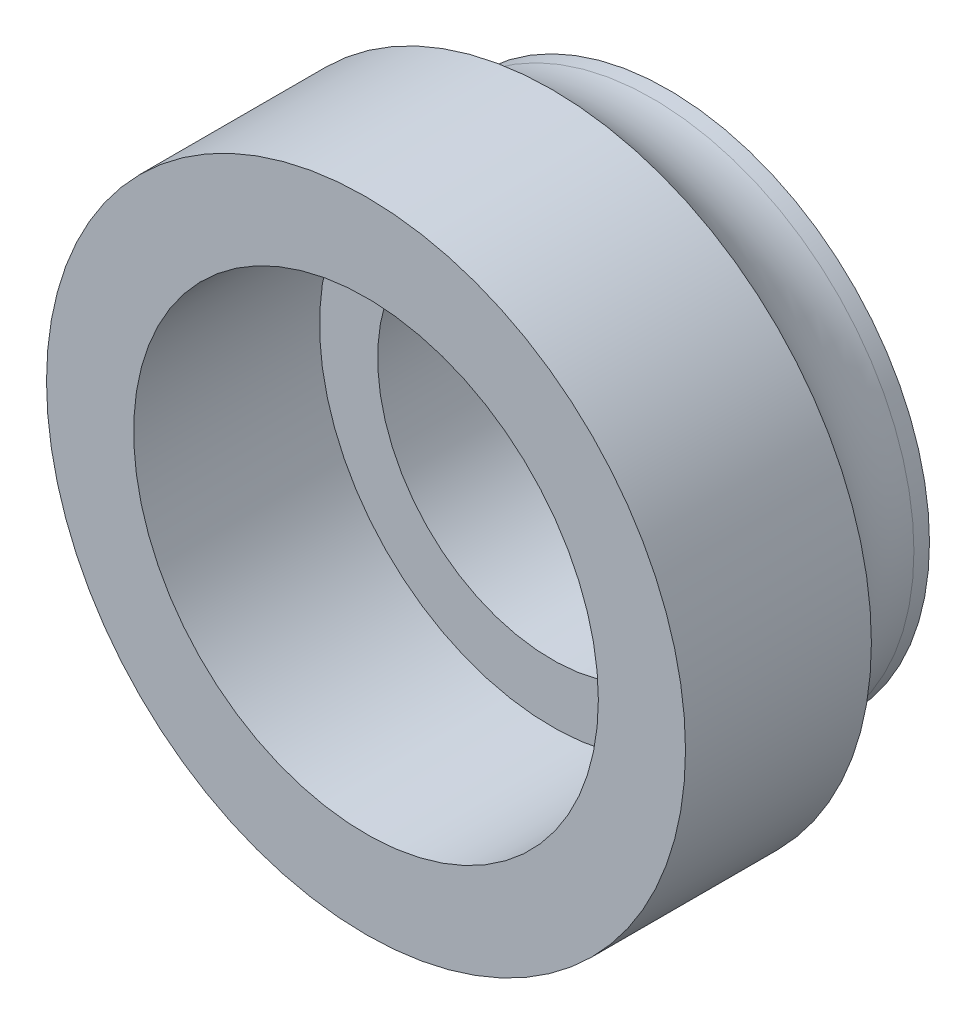
SolidWorks part; units mm, degrees
ref_plane "Alzado" through (0, 0, 0) normal (0, 0, 1) x (1, 0, 0)
ref_plane "Planta" through (0, 0, 0) normal (0, 1, 0) x (1, 0, 0)
ref_plane "Vista lateral" through (0, 0, 0) normal (1, 0, 0) x (0, 0, -1)
sketch "Croquis1" plane through (0, 0, 0) normal (0, 0, 1) x (1, 0, 0)
  circle A0 centre (0, 0) radius 4.5
  circle A1 centre (0, 0) radius 3
  dimension "D1" = 6
  dimension "D2" = 9
extrude "Saliente-Extruir1" add sketch "Croquis1" along normal blind 2
sketch "Croquis2" plane through (0, 0, 2) normal (0, 0, 1) x (1, 0, 0)
  circle A0 centre (0, 0) radius 4
  circle A1 centre (0, 0) radius 5.5
  dimension "D1" = 8
  dimension "D2" = 11
extrude "Saliente-Extruir2" add sketch "Croquis2" along normal blind 3.2
fillet "Redondeo1" radius 2 1 edges at (4.5, 0, 2)
